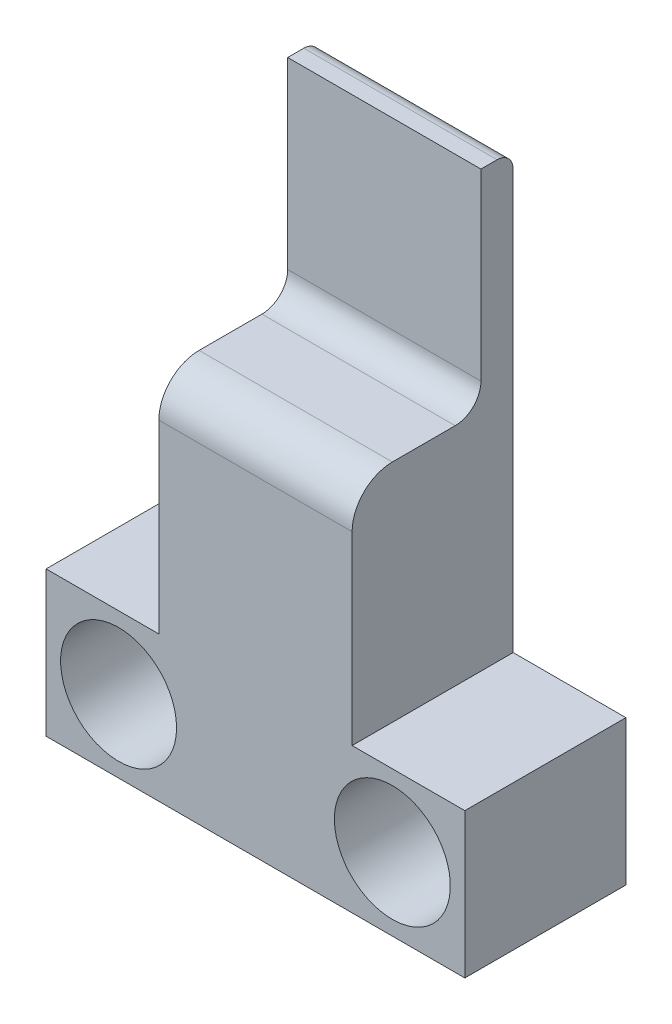
SolidWorks part; units mm, degrees
ref_plane "前视基准面" through (0, 0, 0) normal (0, 0, 1) x (1, 0, 0)
ref_plane "上视基准面" through (0, 0, 0) normal (0, 1, 0) x (1, 0, 0)
ref_plane "右视基准面" through (0, 0, 0) normal (1, 0, 0) x (0, 0, -1)
other "Configuration Table"
sketch "草图1" plane through (0, 0, 0) normal (0, 0, 1) x (1, 0, 0)
  line L1 (-13, 4.5) -> (13, 4.5)
  line L2 (-13, 4.5) -> (-13, -4.5)
  line L3 (-13, -4.5) -> (13, -4.5)
  line L4 (13, 4.5) -> (13, -4.5)
  line L5 (-13, 4.5) -> (13, -4.5) construction
  line L6 (-13, -4.5) -> (13, 4.5) construction
  point P0 (0, 0)
  dimension "D1" = 26
  dimension "D2" = 9
extrude "凸台-拉伸1" add sketch "草图1" against normal blind 10
sketch "草图2" plane through (0, 0, 0) normal (0, 0, 1) x (1, 0, 0)
  line L0 (0, 8.6502) -> (0, -9.0329) construction
  line L1 (-8.5, 8.6502) -> (-8.5, -9.0329) construction
  line L5 (-13, 0) -> (13, 0)
  line L6 (-13, 0) -> (13, 0) construction
  circle A0 centre (-8.5, 0) radius 3.6
  circle A2 centre (8.5, 0) radius 3.6
  dimension "D4" = 7.2
  dimension "D1" = 8.5
  dimension "D3" = 4.5
extrude "切除-拉伸1" cut sketch "草图2" against normal through all
sketch "草图5" plane through (-13, 0, 0) normal (-1, 0, 0) x (0, 0, 1)
  line L0 (0, 4.5) -> (-10, 4.5)
  line L1 (-10, 4.5) -> (-10, 8.3014)
  line L2 (-10, 8.3014) -> (-10, 30.5)
  line L3 (-9, 31.5) -> (-8, 31.5)
  line L4 (-8, 31.5) -> (-8, 20.1)
  line L5 (-6.4, 18.5) -> (-2.5, 18.5)
  line L6 (0, 16) -> (0, 4.5)
  line L7 (-10, 4.5) -> (-10, -4.5) construction
  arc A0 (-9, 31.5) -> (-10, 30.5) centre (-9, 30.5) ccw
  arc A1 (-6.4, 18.5) -> (-8, 20.1) centre (-6.4, 20.1) cw
  arc A2 (0, 16) -> (-2.5, 18.5) centre (-2.5, 16) ccw
  dimension "D4" = 1
  dimension "D5" = 1.6
  dimension "D6" = 2.5
  dimension "D1" = 27
  dimension "D2" = 14
  dimension "D3" = 8
extrude "凸台-拉伸2" add sketch "草图5" against normal through all
extrude "切除-拉伸2" cut sketch "草图5<2>" against normal blind 7
sketch "草图5<2>" plane through (-13, 0, 0) normal (-1, 0, 0) x (0, 0, 1) same geometry as "草图5"
mirror "镜向1" about plane through (0, 0, 0) normal (1, 0, 0) of "切除-拉伸2"
